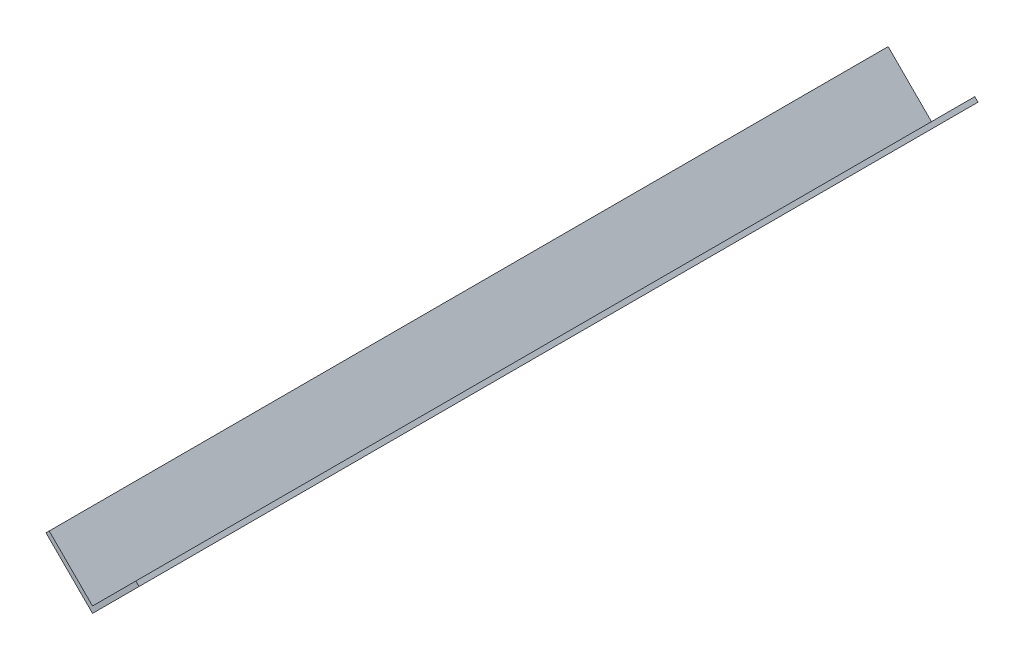
SolidWorks part; units mm, degrees
material "6061 Alloy"
ref_plane "Front Plane" through (0, 0, 0) normal (0, 0, 1) x (1, 0, 0)
ref_plane "Top Plane" through (0, 0, 0) normal (0, 1, 0) x (1, 0, 0)
ref_plane "Right Plane" through (0, 0, 0) normal (1, 0, 0) x (0, 0, -1)
sketch "Sketch1" plane through (0, 0, 0) normal (0, 0, 1) x (1, 0, 0)
  line L0 (0, 0) -> (-17.9605, 17.9605)
  line L1 (-17.9605, 17.9605) -> (-16.7257, 19.1953)
  line L2 (-16.7257, 19.1953) -> (0, 2.4696)
  line L3 (0, 2.4696) -> (16.7257, 19.1953)
  line L4 (16.7257, 19.1953) -> (17.9605, 17.9605)
  line L5 (17.9605, 17.9605) -> (0, 0)
  dimension "D1" = 1.7463
  dimension "D2" = 25.4
extrude "Boss-Extrude1" add sketch "Sketch1" along normal blind 323.85
